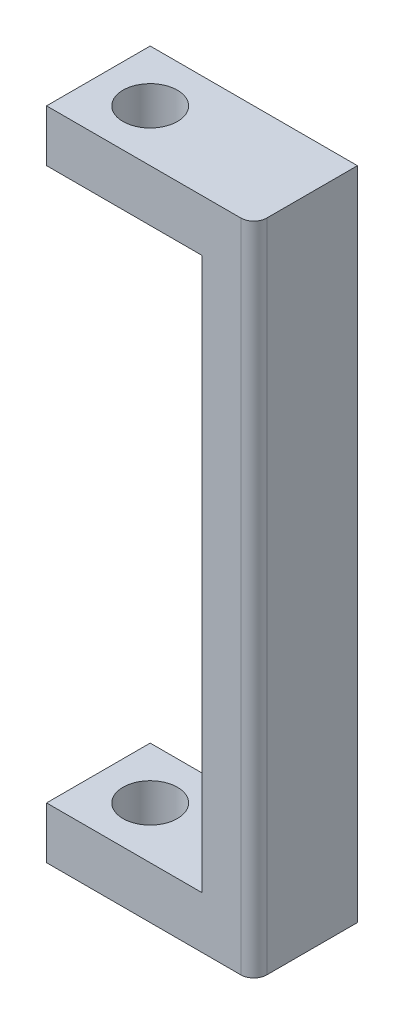
SolidWorks part; units mm, degrees
ref_plane "Front Plane" through (0, 0, 0) normal (0, 0, 1) x (1, 0, 0)
ref_plane "Top Plane" through (0, 0, 0) normal (0, 1, 0) x (1, 0, 0)
ref_plane "Right Plane" through (0, 0, 0) normal (1, 0, 0) x (0, 0, -1)
sketch "Sketch1" plane through (0, 0, 0) normal (0, 1, 0) x (1, 0, 0)
  line L0 (0, 0) -> (-2, 0) construction
  line L1 (-2, 2) -> (4, 2)
  line L2 (-2, 2) -> (-2, -2)
  line L3 (-2, -2) -> (4, -2)
  line L4 (4, 2) -> (4, -2)
  line L5 (0, 0) -> (0, -2) construction
  circle A0 centre (0, 0) radius 1.05
  point P0 (0, 0)
  point P8 (-1.5286, -2.4694)
  point P11 (-2.6038, -2.4694)
  point P12 (0, 0)
  dimension "D3" = 2.1
  dimension "D1" = 6
  dimension "D2" = 4
  dimension "D4" = 2
extrude "Boss-Extrude1" add sketch "Sketch1" along normal blind 2
sketch "Sketch2" plane through (0, 0, 0) normal (0, 1, 0) x (1, 0, 0)
  line L0 (4, -2) -> (6, -2)
  line L2 (6, -2) -> (6, 2)
  line L3 (6, 2) -> (4, 2)
  line L4 (4, -2) -> (4, 2) construction
  line L5 (4, 2) -> (4, -2)
  dimension "D1" = 2
extrude "Boss-Extrude2" add sketch "Sketch2" along normal up to surface (25.3 mm away) up to face at (1, 0, 0)
sketch "Sketch3" plane through (0, 25.3, 0) normal (0, 1, 0) x (1, 0, 0)
  line L0 (4, 2) -> (4, -2) construction
  line L1 (4, 2) -> (-2, 2) construction
  line L2 (-2, 2) -> (-2, -2) construction
  line L3 (-2, -2) -> (4, -2) construction
  line L4 (4, 2) -> (4, -2)
  line L5 (4, 2) -> (-2, 2)
  line L6 (-2, 2) -> (-2, -2)
  line L7 (-2, -2) -> (4, -2)
  circle A0 centre (0, 0) radius 1.05 construction
  circle A1 centre (0, 0) radius 1.05
extrude "Boss-Extrude3" add sketch "Sketch3" against normal blind 2
fillet "Fillet1" radius 0.5 1 edges at (6, 12.65, 2)
